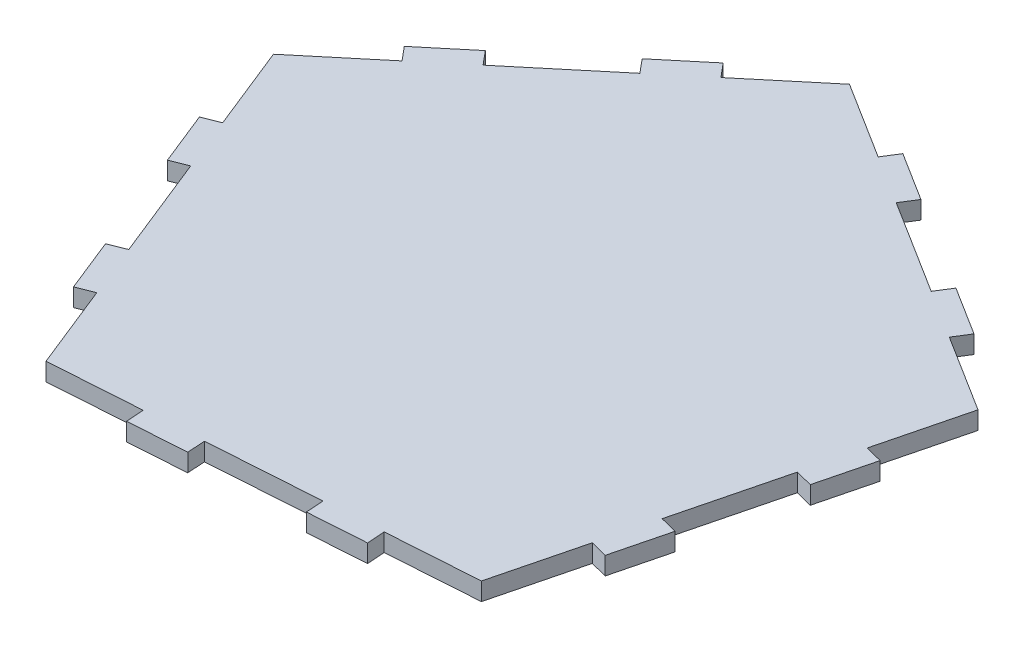
SolidWorks part; units mm, degrees
ref_plane "Front Plane" through (0, 0, 0) normal (0, 0, 1) x (1, 0, 0)
ref_plane "Top Plane" through (0, 0, 0) normal (0, 1, 0) x (1, 0, 0)
ref_plane "Right Plane" through (0, 0, 0) normal (1, 0, 0) x (0, 0, -1)
sketch "Sketch1" plane through (0, 0, 0) normal (0, 1, 0) x (1, 0, 0)
  line L1 (-63.7371, 16.0796) -> (-34.9884, -55.6487)
  line L2 (-34.9884, -55.6487) -> (42.1131, -50.4724)
  line L3 (42.1131, -50.4724) -> (61.0157, 24.4551)
  line L4 (61.0157, 24.4551) -> (-4.4033, 65.5865)
  line L5 (-4.4033, 65.5865) -> (-63.7371, 16.0796)
  circle A0 centre (0, 0) radius 53.18 construction
  dimension "D1" = 106.36
extrude "Boss-Extrude1" add sketch "Sketch1" along normal blind 3.18
sketch "Sketch2" plane through (0, 0, 0) normal (0, -1, 0) x (1, 0, 0)
  line L0 (-56.7625, 1.3223) -> (-53.8107, 0.1392)
  line L1 (-56.7625, 1.3223) -> (-53.124, 10.4003)
  line L2 (-53.8107, 0.1392) -> (-50.1723, 9.2172)
  line L3 (-53.124, 10.4003) -> (-50.1723, 9.2172)
  line L4 (-63.7371, -16.0796) -> (-34.9884, 55.6487) construction
  line L5 (-45.6015, 29.1689) -> (-41.9631, 38.2469)
  line L6 (-45.6015, 29.1689) -> (-42.6498, 27.9858)
  line L7 (-41.9631, 38.2469) -> (-39.0113, 37.0638)
  line L8 (-42.6498, 27.9858) -> (-39.0113, 37.0638)
  line L9 (-49.3628, 19.7846) -> (-19.2439, 7.7129) construction
  line L10 (-43.7823, 33.7079) -> (-40.8306, 32.5248) construction
  dimension "D1" = 3.18
  dimension "D2" = 9.78
  dimension "D3" = 10.11
extrude "Cut-Extrude1" [suppressed] cut sketch "Sketch2" against normal through all
ref_axis "Axis1" through (0, 3.339, 0) along (0, -1, 0)
pattern_circular "CirPattern1" [suppressed] count 5 over 360 about axis through (0, 3.339, 0) along (0, -1, 0) of bodies 102
sketch "Sketch3" plane through (0, 3.18, 0) normal (0, 1, 0) x (1, 0, 0)
  line L0 (0, 0) -> (-40.9819, 49.1167) construction
  line L1 (-49.5112, 27.9494) -> (-47.4739, 25.5077)
  line L2 (-49.5112, 27.9494) -> (-41.664, 34.4969)
  line L3 (-47.4739, 25.5077) -> (-39.6267, 32.0552)
  line L4 (-41.664, 34.4969) -> (-39.6267, 32.0552)
  line L5 (-4.4033, 65.5865) -> (-63.7371, 16.0796) construction
  line L6 (-74.0334, 7.4886) -> (-71.9961, 5.0469)
  line L7 (-74.0334, 7.4886) -> (2.7493, 71.5544)
  line L8 (-71.9961, 5.0469) -> (4.7866, 69.1127)
  line L9 (2.7493, 71.5544) -> (4.7866, 69.1127)
  line L14 (-26.4764, 47.1691) -> (-24.4391, 44.7274)
  line L15 (-26.4764, 47.1691) -> (-18.6292, 53.7166)
  line L16 (-24.4391, 44.7274) -> (-16.5919, 51.275)
  line L17 (-18.6292, 53.7166) -> (-16.5919, 51.275)
  line L18 (-45.5876, 31.2231) -> (-43.5503, 28.7815) construction
  line L20 (-9.7247, 57.0048) -> (-11.762, 59.4465) construction
  line M18 (-4.4033, 65.5865) -> (-63.7371, 16.0796)
  line M19 (-63.7371, 16.0796) -> (-34.9884, -55.6487)
  line M22 (61.0157, 24.4551) -> (-4.4033, 65.5865)
  dimension "D1" = 3.18
  dimension "D2" = 10.22
  dimension "D3" = 9.89
  dimension "D4" = 100
extrude "Cut-Extrude2" cut sketch "Sketch3" against normal blind 10 contours L8 L1 M19 M18 | L14 L7 L4 L8 | L17 L8 M18 M22 region at (-55.7964, 3.18, -20.6156) region at (-33.0515, 3.18, -39.6122) region at (-10.2882, 3.18, -58.5866)
pattern_circular "CirPattern2" count 5 over 360 about axis through (0, 3.339, 0) along (0, -1, 0) of "Cut-Extrude2"
equation "\"kerf\"= .22mm"
equation "\"tabWidthF\"= 10 - \"kerf\""
equation "\"tabThickness\"= 3.18"
equation "\"D1@Sketch2\"=\"tabThickness\""
equation "\"tabWidthM\"= 10 + \"kerf\""
equation "\"halfkerf\" = \"kerf\" / 2.00mm"
equation "\"tabLength\" = \"kerf\" + 12"
